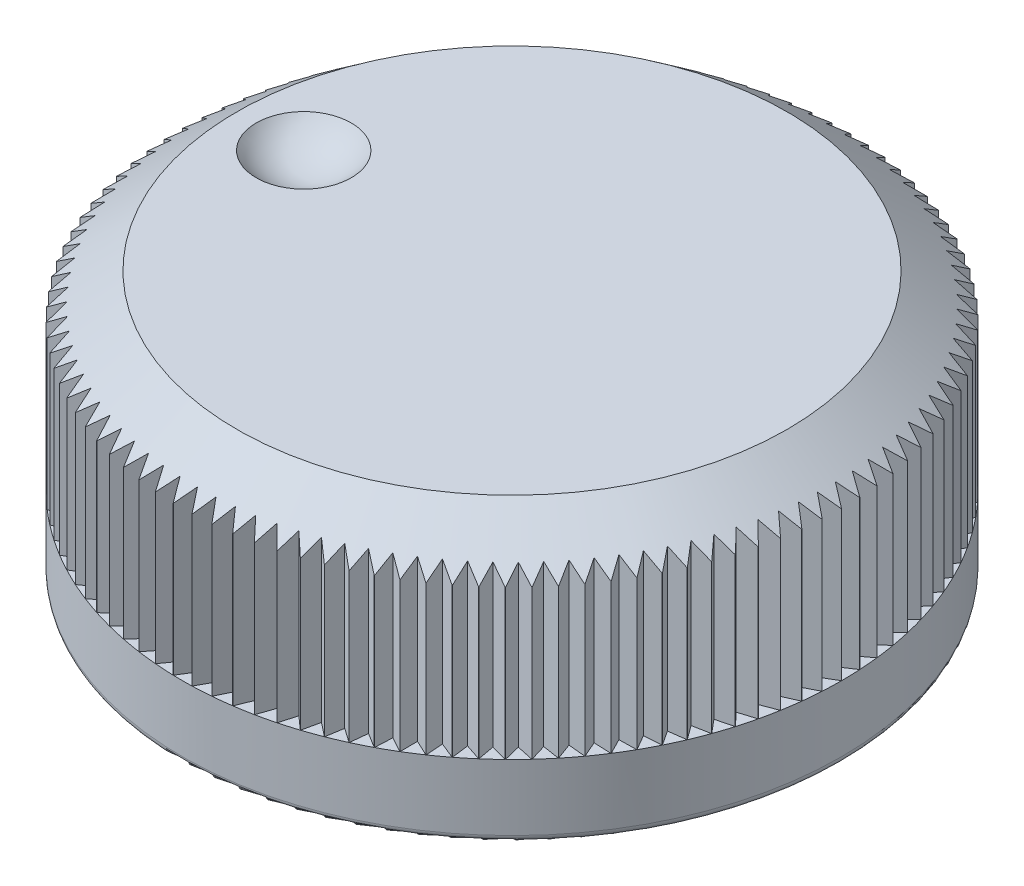
SolidWorks part; units mm, degrees
ref_plane "Front Plane" through (0, 0, 0) normal (0, 0, 1) x (1, 0, 0)
ref_plane "Top Plane" through (0, 0, 0) normal (0, 1, 0) x (1, 0, 0)
ref_plane "Right Plane" through (0, 0, 0) normal (1, 0, 0) x (0, 0, -1)
ref_axis "Axis1" through (0, 12.6, 0) along (0, -1, 0)
sketch "Sketch1" plane through (0, 0, 0) normal (0, 0, 1) x (1, 0, 0)
  line L0 (0, 16) -> (0, 18) construction
  line L1 (0, 18) -> (18.7867, 18)
  line L2 (18.7867, 18) -> (22.5, 15.1648)
  line L3 (22.5, 15.1648) -> (22.5, 0)
  line L4 (22.5, 0) -> (15.8336, 0)
  line L5 (3, 3) -> (3, 16)
  line L6 (3, 16) -> (0, 16)
  line L7 (0, 18) -> (0, 16)
  line L8 (3, 3) -> (15.8336, 3)
  line L9 (15.8336, 3) -> (15.8336, 0)
  point P6 (22.5, 15.1648)
  dimension "D1" = 3
  dimension "D2" = 2
  dimension "D3" = 22.5
  dimension "D4" = 18
  dimension "D5" = 13
revolve "Revolve1" add sketch "Sketch1" angle 360 about L0
sketch "Sketch3" plane through (0, 0, 0) normal (0, 0, 1) x (1, 0, 0)
  line L0 (-18.2202, 20.3383) -> (-10.2202, 20.3383)
  arc A0 (-18.2202, 20.3383) -> (-10.2202, 20.3383) centre (-14.2202, 20.3383) ccw
  point P1 (-13.823, 21.0326)
  point P4 (-14.2202, 20.3383)
  dimension "D1" = 4
revolve "Cut-Revolve1" cut sketch "Sketch3" angle 360 about L0
sketch "Sketch4" plane through (0, 0, 0) normal (0, 1, 0) x (1, 0, 0)
  line L0 (0, 22.5) -> (0, 0) construction
  line L1 (-1, 23.0678) -> (0, 21.4748)
  line L2 (0, 21.4748) -> (1, 23.0678)
  line L3 (1, 23.0678) -> (-1, 23.0678)
  circle A0 centre (0, 0) radius 22.5 construction
  point P9 (0, 23.0678)
extrude "Cut-Extrude1" cut sketch "Sketch4" along normal through all from offset 5
pattern_circular "CirPattern1" count 110 over 360 about axis through (0, 12.6, 0) along (0, -1, 0) of "Cut-Extrude1"
sketch "Sketch5" plane through (0, 3, 0) normal (0, -1, 0) x (1, 0, 0)
  line L1 (-4.567, 4.1031) -> (6.1495, 4.1031)
  line L2 (-4.567, 4.1031) -> (-4.567, 2.0248)
  line L3 (-4.567, 2.0248) -> (6.1495, 2.0248)
  line L4 (6.1495, 4.1031) -> (6.1495, 2.0248)
extrude "Boss-Extrude1" add sketch "Sketch5" against normal blind 14
fillet "Fillet1" radius 0.5 4 edges at (15.8336, 0, 0) (22.5, 0, 0) (0, 3, -3) (0, 3, 2.0248)
